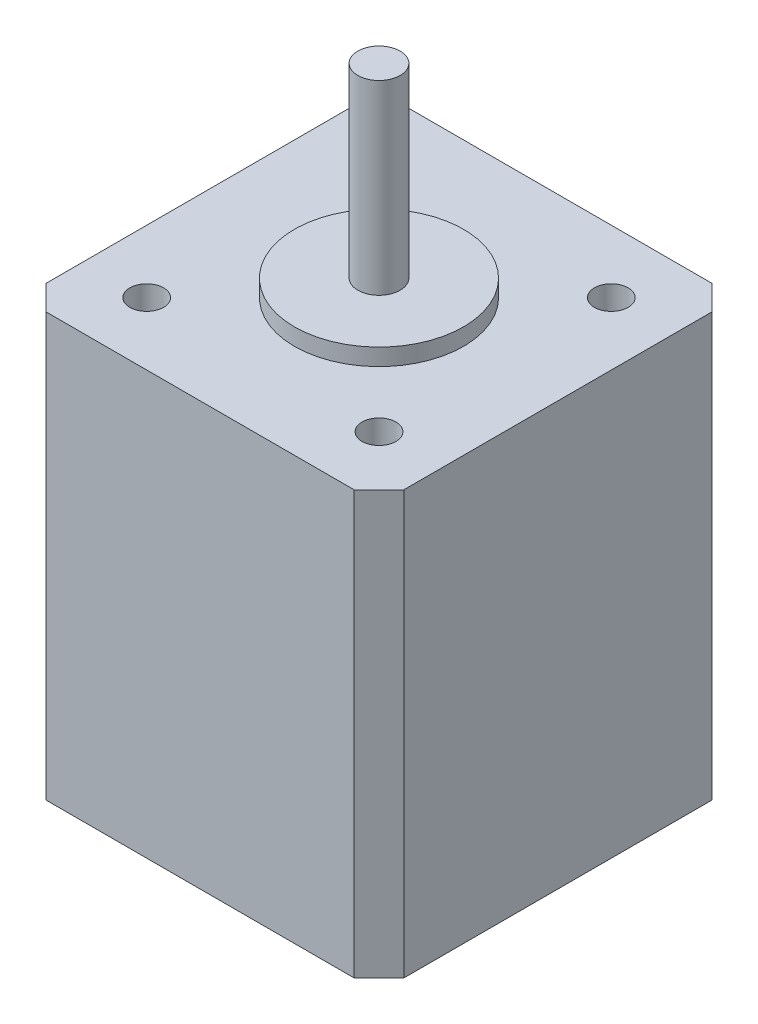
SolidWorks part; units mm, degrees
ref_plane "前视基准面" through (0, 0, 0) normal (0, 0, 1) x (1, 0, 0)
ref_plane "上视基准面" through (0, 0, 0) normal (0, 1, 0) x (1, 0, 0)
ref_plane "右视基准面" through (0, 0, 0) normal (1, 0, 0) x (0, 0, -1)
sketch "草图1" plane through (0, 0, 0) normal (0, 1, 0) x (1, 0, 0)
  line L0 (-16.1376, -21.639) -> (-16.1376, 14.7928)
  line L5 (-13.2035, 17.7269) -> (23.2283, 17.7269)
  line L6 (-13.2035, -24.5731) -> (23.2283, -24.5731)
  line L7 (26.1624, -21.639) -> (26.1624, 14.7928)
  line L8 (-16.1376, -21.639) -> (-13.2035, -24.5731)
  line L9 (26.1624, -21.639) -> (23.2283, -24.5731)
  line L10 (23.2283, 17.7269) -> (26.1624, 14.7928)
  line L11 (-16.1376, 14.7928) -> (-13.2035, 17.7269)
  circle A0 centre (5.0124, -3.4231) radius 10
  circle A1 centre (-8.7226, -17.1581) radius 2
  circle A2 centre (-8.7226, 10.3119) radius 2
  circle A3 centre (18.7474, -17.1581) radius 2
  circle A4 centre (18.7474, 10.3119) radius 2
  point P5 (4.0344, -77.9983)
  point P7 (5.0124, -3.4231)
  point P19 (-11.3085, -19.7441)
  point P26 (-11.3085, -19.7441)
  point P27 (-8.7226, 10.3119)
  point P28 (21.3334, -19.7441)
  point P29 (21.3334, 12.8978)
  dimension "D3" = 27.47
  dimension "D4" = 27.47
  dimension "D5" = 4
  dimension "D1" = 42.3
  dimension "D2" = 42.3
extrude "凸台-拉伸2" add sketch "草图1" along normal blind 2 contours A0 region at (5.0124, 0, 3.4231)
extrude "凸台-拉伸5" add sketch "草图1<6>" against normal blind 50 contours L5 L10 L7 L9 L6 L8 L0 L11 | A1 | A2 | A4 | A3
sketch "草图1<6>" plane through (0, 0, 0) normal (0, 1, 0) x (1, 0, 0) same geometry as "草图1"
sketch "草图8" plane through (0, 0, -17.7269) normal (0, 0, -1) x (-1, 0, 0)
  line L0 (-23.2283, -50) -> (-8.2283, -50) construction
  line L1 (13.2035, -50) -> (-23.2283, -50) construction
  line L2 (-8.2283, -50) -> (-1.7965, -50) construction
  line L3 (-1.7965, -50) -> (13.2035, -50) construction
  line L4 (-8.2283, -50) -> (-8.2283, -45.3103)
  line L5 (-8.2283, -45.3103) -> (-1.7965, -45.3103)
  line L6 (-1.7965, -45.3103) -> (-1.7965, -50)
  line L7 (-7.3416, -46.1454) -> (-7.3416, -49.336)
  line L8 (-7.3416, -49.336) -> (-2.8299, -49.336)
  line L9 (-2.8299, -49.336) -> (-2.8299, -46.1454)
  line L10 (-2.8299, -46.1454) -> (-7.3416, -46.1454)
  line L11 (13.2035, 0) -> (-23.2283, 0)
  line L12 (-23.2283, 0) -> (-23.2283, -50)
  line L13 (-23.2283, -50) -> (13.2035, -50)
  line L14 (13.2035, -50) -> (13.2035, 0)
  line L17 (-8.2283, -50) -> (-1.7965, -50)
  dimension "D1" = 15
  dimension "D2" = 15
  dimension "D3" = 0
extrude "凸台-拉伸7" add sketch "草图8" along normal blind 5
sketch "草图10" plane through (0, 0, -17.7269) normal (0, 0, -1) x (-1, 0, 0)
  circle A0 centre (-6.5973, -47.7693) radius 0.2
  circle A1 centre (-5.5213, -47.7693) radius 0.2
  circle A2 centre (-4.5747, -47.7693) radius 0.2
  circle A3 centre (-3.5906, -47.7693) radius 0.2
extrude "凸台-拉伸8" add sketch "草图10" along normal blind 4
sketch "草图11" plane through (0, 2, 0) normal (0, 1, 0) x (1, 0, 0)
  circle A1 centre (5.0124, -3.4231) radius 2.5
extrude "凸台-拉伸9" add sketch "草图11" along normal blind 22
